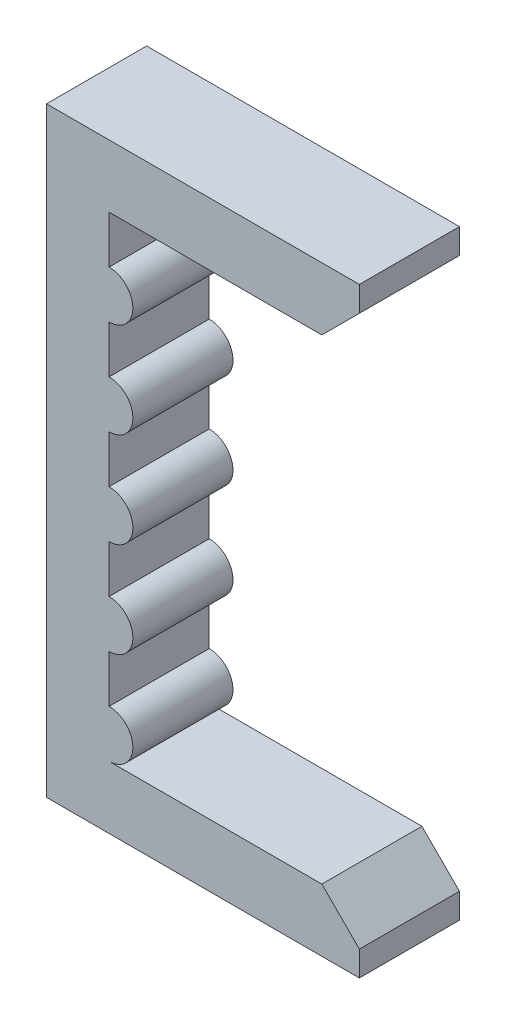
SolidWorks part; units mm, degrees
ref_plane "Front Plane" through (0, 0, 0) normal (0, 0, 1) x (1, 0, 0)
ref_plane "Top Plane" through (0, 0, 0) normal (0, 1, 0) x (1, 0, 0)
ref_plane "Right Plane" through (0, 0, 0) normal (1, 0, 0) x (0, 0, -1)
sketch "Sketch1" plane through (0, 0, 0) normal (0, 0, 1) x (1, 0, 0)
  line L0 (0, 0) -> (0, 48)
  line L1 (0, 48) -> (25, 48)
  line L2 (25, 48) -> (25, 43)
  line L3 (25, 43) -> (5, 43)
  line L4 (5, 43) -> (5, 5)
  line L5 (5, 5) -> (25, 5)
  line L6 (25, 5) -> (25, 0)
  line L7 (25, 0) -> (0, 0)
  circle A0 centre (5, 6.9) radius 1.9
  dimension "D4" = 3.8
  dimension "D1" = 5
  dimension "D2" = 5
  dimension "D3" = 38
  dimension "D5" = 20
extrude "Boss-Extrude1" add sketch "Sketch1" along normal blind 8 contours L4 L5 L6 L7 L0 L1 L2 L3
extrude "Boss-Extrude2" add sketch "Sketch1<3>" along normal up to surface (8 mm away) contours A0 up to face at (13.75, 24, 8)
sketch "Sketch1<3>" plane through (0, 0, 0) normal (0, 0, 1) x (1, 0, 0) same geometry as "Sketch1"
pattern_linear "LPattern1" count 5 spacing 7.6 along (0, 1, 0) of "Boss-Extrude2"
chamfer "Chamfer1" distance 3 angle 45 2 edges at (25, 5, 4) (25, 43, 4)
